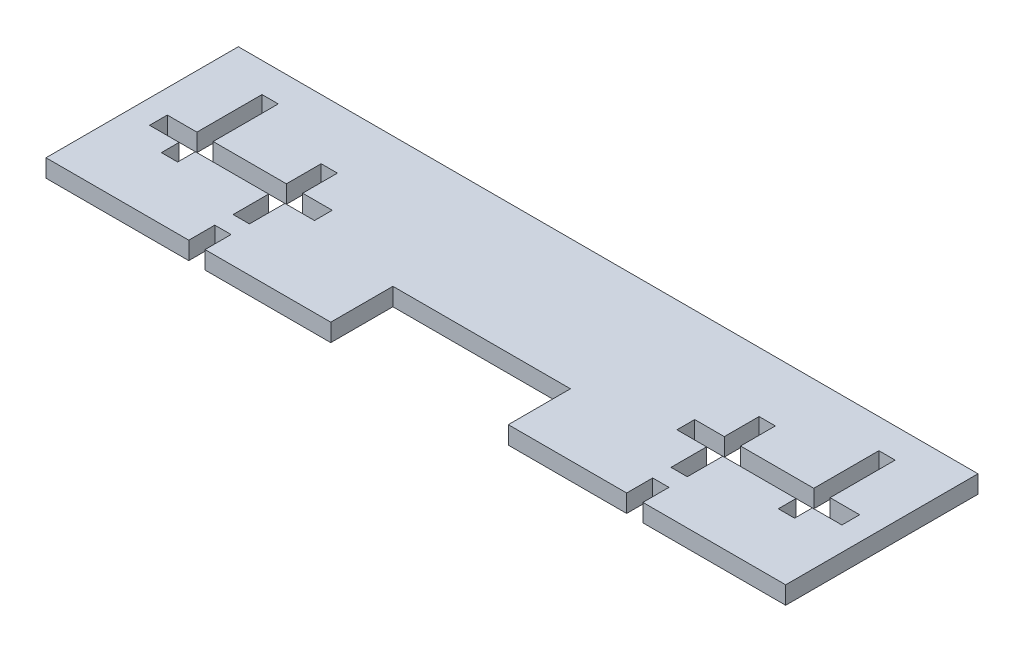
SolidWorks part; units mm, degrees
ref_plane "Front" through (0, 0, 0) normal (0, 0, 1) x (1, 0, 0)
ref_plane "Top" through (0, 0, 0) normal (0, 1, 0) x (1, 0, 0)
ref_plane "Right" through (0, 0, 0) normal (1, 0, 0) x (0, 0, -1)
sketch "Sketch1" plane through (0, 0, 0) normal (0, 1, 0) x (1, 0, 0)
  line L1 (0, 0) -> (250, 0)
  line L2 (0, 0) -> (0, 65)
  line L3 (0, 65) -> (250, 65)
  line L4 (250, 0) -> (250, 65)
  dimension "D1" = 65
  dimension "D2" = 250
extrude "Boss-Extrude1" add sketch "Sketch1" along normal blind 6
sketch "Sketch2" plane through (0, 6, 0) normal (0, 1, 0) x (1, 0, 0)
  line L0 (125, 65) -> (125, 0) construction
  line L1 (18, 55) -> (23.5, 55)
  line L2 (18, 55) -> (18, 21)
  line L3 (18, 21) -> (23.5, 21)
  line L4 (23.5, 55) -> (23.5, 21)
  line L5 (48.25, 44.75) -> (53.75, 44.75)
  line L6 (48.25, 44.75) -> (48.25, -2.75)
  line L7 (48.25, -2.75) -> (53.75, -2.75)
  line L8 (53.75, 44.75) -> (53.75, -2.75)
  line L9 (250, 65) -> (0, 65) construction
  line L10 (0, 0) -> (250, 0) construction
  line L11 (0, 32.5) -> (125, 32.5) construction
  line L12 (0, 65) -> (0, 0) construction
  line L13 (196.25, 44.75) -> (196.25, -2.75)
  line L14 (201.75, -2.75) -> (196.25, -2.75)
  line L15 (201.75, 44.75) -> (201.75, -2.75)
  line L16 (201.75, 44.75) -> (196.25, 44.75)
  line L17 (226.5, 55) -> (226.5, 21)
  line L18 (232, 21) -> (226.5, 21)
  line L19 (232, 55) -> (232, 21)
  line L20 (232, 55) -> (226.5, 55)
  point P14 (18, 38)
  dimension "D1" = 107
  dimension "D2" = 24.75
  dimension "D3" = 47.5
  dimension "D4" = 34
  dimension "D5" = 5.5
  dimension "D6" = 10.25
  dimension "D7" = 10
extrude "Cut-Extrude1" cut sketch "Sketch2" against normal through all
sketch "Sketch3" plane through (0, 6, 0) normal (0, 1, 0) x (1, 0, 0)
  line L0 (0, 0) -> (48.25, 0) construction
  line L1 (156.25, 0) -> (96.25, 0)
  line L2 (156.25, 0) -> (156.25, 21)
  line L3 (156.25, 21) -> (96.25, 21)
  line L4 (96.25, 0) -> (96.25, 21)
  line L5 (196.25, 44.75) -> (196.25, 0) construction
  line L6 (18, 21) -> (23.5, 21) construction
  dimension "D1" = 40
  dimension "D2" = 60
extrude "Cut-Extrude2" cut sketch "Sketch3" against normal through all
sketch "Sketch4" plane through (0, 6, 0) normal (0, 1, 0) x (1, 0, 0)
  line L1 (8, 33) -> (63.75, 33)
  line L2 (8, 33) -> (8, 27)
  line L3 (8, 27) -> (63.75, 27)
  line L4 (63.75, 33) -> (63.75, 27)
  line L6 (18, 21) -> (23.5, 21) construction
  line L7 (53.75, 0) -> (53.75, 44.75) construction
  line L8 (18, 55) -> (18, 21) construction
  dimension "D1" = 6
  dimension "D2" = 6
  dimension "D3" = 10
  dimension "D4" = 10
extrude "Cut-Extrude3" cut sketch "Sketch4" against normal through all
sketch "Sketch5" plane through (0, 6, 0) normal (0, 1, 0) x (1, 0, 0)
  line L0 (48.25, 27) -> (48.25, 0) construction
  line L1 (48.25, 15) -> (53.75, 15)
  line L2 (48.25, 15) -> (48.25, 8.8)
  line L3 (48.25, 8.8) -> (53.75, 8.8)
  line L4 (53.75, 15) -> (53.75, 8.8)
  line L5 (53.75, 0) -> (53.75, 27) construction
  line L6 (53.75, 27) -> (63.75, 27) construction
  dimension "D1" = 6.2
  dimension "D2" = 12
extrude "Boss-Extrude2" add sketch "Sketch5" against normal blind 6
ref_plane "Plane1" through (125, 0, 0) normal (1, 0, 0) x (0, 0, -1)
mirror "Mirror1" about plane through (125, 0, 0) normal (1, 0, 0) of "Cut-Extrude3", "Boss-Extrude2"
